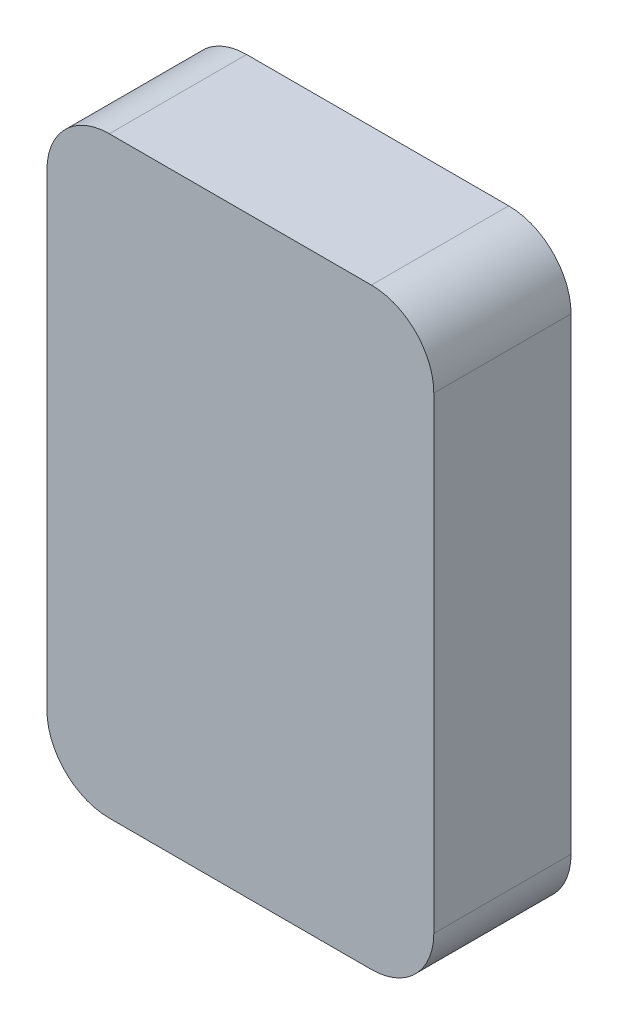
SolidWorks part; units mm, degrees
ref_plane "Ön Düzlem" through (0, 0, 0) normal (0, 0, 1) x (1, 0, 0)
ref_plane "Üst Düzlem" through (0, 0, 0) normal (0, 1, 0) x (1, 0, 0)
ref_plane "Sağ Düzlem" through (0, 0, 0) normal (1, 0, 0) x (0, 0, -1)
sketch "Çizim1" plane through (0, 0, 0) normal (0, 0, 1) x (1, 0, 0)
  line L0 (-31, 47.5) -> (31, -47.5) construction
  line L1 (-31, 47.5) -> (31, 47.5)
  line L2 (-31, 47.5) -> (-31, -47.5)
  line L3 (-31, -47.5) -> (31, -47.5)
  line L4 (31, 47.5) -> (31, -47.5)
  dimension "D1" = 95
  dimension "D2" = 62
extrude "Yükseklik-Ekstrüzyon1" add sketch "Çizim1" along normal blind 22
fillet "Radyus1" radius 10 4 edges at (-31, -47.5, 11) (31, -47.5, 11) (31, 47.5, 11) (-31, 47.5, 11)
